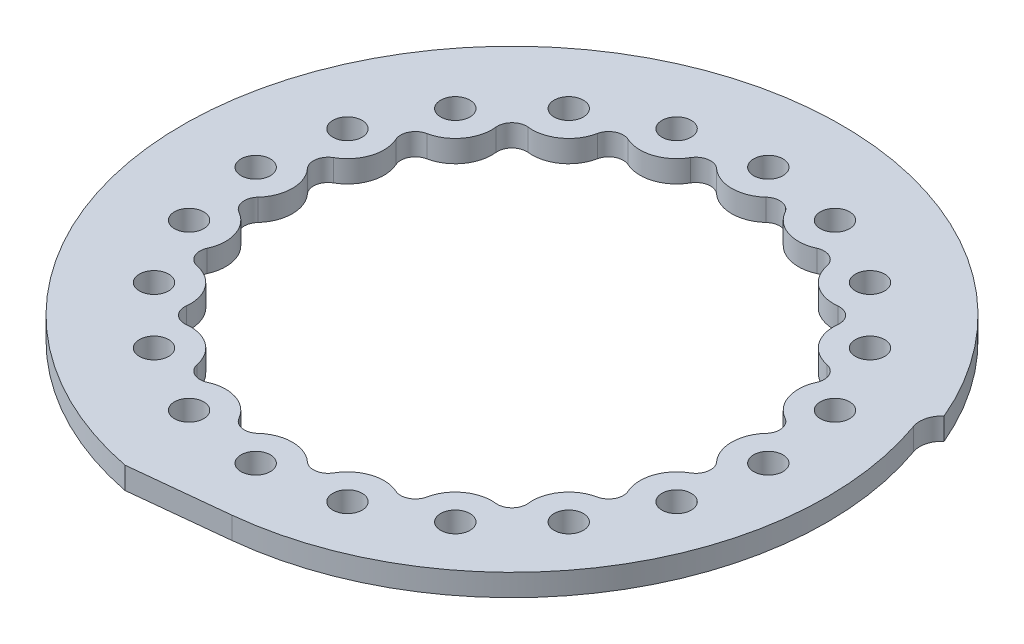
SolidWorks part; units mm, degrees
material "POM Acetal Copolymer"
ref_plane "Front Plane" through (0, 0, 0) normal (0, 0, 1) x (1, 0, 0)
ref_plane "Top Plane" through (0, 0, 0) normal (0, 1, 0) x (1, 0, 0)
ref_plane "Right Plane" through (0, 0, 0) normal (1, 0, 0) x (0, 0, -1)
sketch "Sketch1" plane through (0, 0, 0) normal (0, 1, 0) x (1, 0, 0)
  circle A0 centre (0, 0) radius 60
  circle A1 centre (0, 0) radius 102.5
  dimension "D1" = 120
  dimension "D2" = 205
extrude "Boss-Extrude1" add sketch "Sketch1" along normal blind 6
sketch "Sketch2" plane through (0, 6, 0) normal (0, 1, 0) x (1, 0, 0)
  circle A0 centre (0, 70) radius 4
  circle A1 centre (0, 0) radius 70 construction
  dimension "D1" = 140
  dimension "D2" = 8
extrude "Cut-Extrude1" cut sketch "Sketch2" against normal through all
pattern_circular "CirPattern1" count 20 over 360 about axis through (0, 6, 0) along (0, -1, 0) of "Cut-Extrude1"
sketch "Sketch3" plane through (0, 6, 0) normal (0, 1, 0) x (1, 0, 0)
  line L0 (0, 0) -> (76.9697, -46.644) construction
  line L1 (0, 0) -> (87.353, 0) construction
  line L3 (70.3733, -57.5291) -> (83.5662, -35.7588) construction
  circle A0 centre (83.5662, -35.7588) radius 6.5
  circle A1 centre (70.3733, -57.5291) radius 6.5
  dimension "D1" = 13
  dimension "D2" = 90
  dimension "D3" = 25.4558
  dimension "D4" = 31.216
extrude "Cut-Extrude2" [suppressed] cut sketch "Sketch3" against normal blind 6
sketch "Sketch4" plane through (0, 6, 0) normal (0, 1, 0) x (1, 0, 0)
  circle A0 centre (0, 0) radius 86
  dimension "D1" = 86
extrude "Cut-Extrude3" cut sketch "Sketch4" against normal through all flip side to cut
sketch "Sketch5" plane through (0, 6, 0) normal (0, 1, 0) x (1, 0, 0)
  arc A40 (46.6947, 42.27) -> (54.6307, 31.3471) centre (56.6312, 41.145) ccw
  arc A41 (57.4714, 25.7718) -> (54.6307, 31.3471) centre (53.8304, 27.428) ccw
  arc A42 (57.4714, 25.7718) -> (61.6436, 12.9311) centre (66.574, 21.6312) ccw
  arc A43 (62.6225, 6.7507) -> (61.6436, 12.9311) centre (59.6715, 9.451) ccw
  arc A44 (62.6225, 6.7507) -> (62.6225, -6.7507) centre (70, 0) ccw
  arc A45 (61.6436, -12.9311) -> (62.6225, -6.7507) centre (59.6715, -9.451) ccw
  arc A46 (61.6436, -12.9311) -> (57.4714, -25.7718) centre (66.574, -21.6312) ccw
  arc A47 (54.6307, -31.3471) -> (57.4714, -25.7718) centre (53.8304, -27.428) ccw
  arc A48 (54.6307, -31.3471) -> (46.6947, -42.27) centre (56.6312, -41.145) ccw
  arc A49 (42.27, -46.6947) -> (46.6947, -42.27) centre (42.7201, -42.7201) ccw
  arc A50 (42.27, -46.6947) -> (31.3471, -54.6307) centre (41.145, -56.6312) ccw
  arc A51 (25.7718, -57.4714) -> (31.3471, -54.6307) centre (27.428, -53.8304) ccw
  arc A52 (25.7718, -57.4714) -> (12.9311, -61.6436) centre (21.6312, -66.574) ccw
  arc A53 (6.7507, -62.6225) -> (12.9311, -61.6436) centre (9.451, -59.6715) ccw
  arc A54 (6.7507, -62.6225) -> (-6.7507, -62.6225) centre (0, -70) ccw
  arc A55 (-12.9311, -61.6436) -> (-6.7507, -62.6225) centre (-9.451, -59.6715) ccw
  arc A56 (-12.9311, -61.6436) -> (-25.7718, -57.4714) centre (-21.6312, -66.574) ccw
  arc A57 (-31.3471, -54.6307) -> (-25.7718, -57.4714) centre (-27.428, -53.8304) ccw
  arc A58 (-31.3471, -54.6307) -> (-42.27, -46.6947) centre (-41.145, -56.6312) ccw
  arc A59 (-46.6947, -42.27) -> (-42.27, -46.6947) centre (-42.7201, -42.7201) ccw
  arc A60 (-46.6947, -42.27) -> (-54.6307, -31.3471) centre (-56.6312, -41.145) ccw
  arc A61 (-57.4714, -25.7718) -> (-54.6307, -31.3471) centre (-53.8304, -27.428) ccw
  arc A62 (-57.4714, -25.7718) -> (-61.6436, -12.9311) centre (-66.574, -21.6312) ccw
  arc A63 (-62.6225, -6.7507) -> (-61.6436, -12.9311) centre (-59.6715, -9.451) ccw
  arc A64 (-62.6225, -6.7507) -> (-62.6225, 6.7507) centre (-70, 0) ccw
  arc A65 (-61.6436, 12.9311) -> (-62.6225, 6.7507) centre (-59.6715, 9.451) ccw
  arc A66 (-61.6436, 12.9311) -> (-57.4714, 25.7718) centre (-66.574, 21.6312) ccw
  arc A67 (-54.6307, 31.3471) -> (-57.4714, 25.7718) centre (-53.8304, 27.428) ccw
  arc A68 (-54.6307, 31.3471) -> (-46.6947, 42.27) centre (-56.6312, 41.145) ccw
  arc A69 (-42.27, 46.6947) -> (-46.6947, 42.27) centre (-42.7201, 42.7201) ccw
  arc A70 (-42.27, 46.6947) -> (-31.3471, 54.6307) centre (-41.145, 56.6312) ccw
  arc A71 (-25.7718, 57.4714) -> (-31.3471, 54.6307) centre (-27.428, 53.8304) ccw
  arc A72 (-25.7718, 57.4714) -> (-12.9311, 61.6436) centre (-21.6312, 66.574) ccw
  arc A73 (-6.7507, 62.6225) -> (-12.9311, 61.6436) centre (-9.451, 59.6715) ccw
  arc A74 (-6.7507, 62.6225) -> (6.7507, 62.6225) centre (0, 70) ccw
  arc A75 (12.9311, 61.6436) -> (6.7507, 62.6225) centre (9.451, 59.6715) ccw
  arc A76 (12.9311, 61.6436) -> (25.7718, 57.4714) centre (21.6312, 66.574) ccw
  arc A77 (31.3471, 54.6307) -> (25.7718, 57.4714) centre (27.428, 53.8304) ccw
  arc A78 (31.3471, 54.6307) -> (42.27, 46.6947) centre (41.145, 56.6312) ccw
  arc A79 (46.6947, 42.27) -> (42.27, 46.6947) centre (42.7201, 42.7201) ccw
extrude "Cut-Extrude4" cut sketch "Sketch5" against normal blind 10
sketch "Sketch6" plane through (0, 6, 0) normal (0, 1, 0) x (1, 0, 0)
  line L0 (-17.3982, -88.3023) -> (8.9894, -85.5289)
  line L1 (82.8454, 35.1658) -> (79.1634, 33.6029)
  line L2 (8.9894, -85.5289) -> (24.1369, -85.5289) construction
  arc A0 (-17.3982, -88.3023) -> (82.8454, 35.1658) centre (0, 0) cw
  circle A1 centre (0, 0) radius 86 construction
  arc A2 (79.1634, 33.6029) -> (8.9894, -85.5289) centre (0, 0) ccw
  dimension "D1" = 90
  dimension "D2" = 6
  dimension "D3" = 17
extrude "Boss-Extrude2" add sketch "Sketch6" against normal up to surface (6 mm away) up to face at (0, 0, -66)
fillet "Fillet1" radius 6 1 edges at (79.1634, 3, -33.6029)
